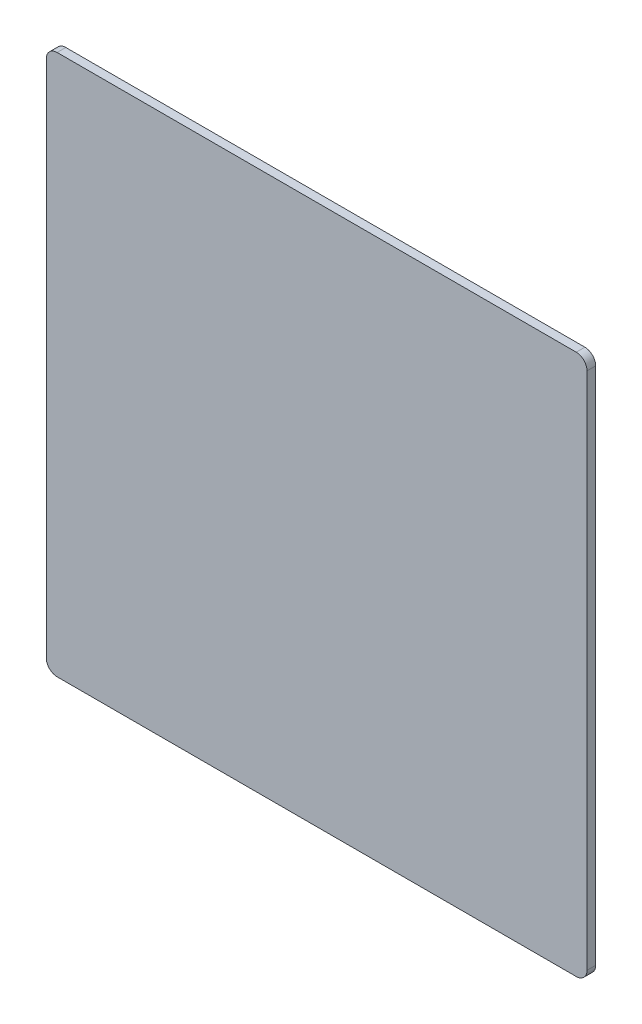
SolidWorks part; units mm, degrees
ref_plane "前视基准面" through (0, 0, 0) normal (0, 0, 1) x (1, 0, 0)
ref_plane "上视基准面" through (0, 0, 0) normal (0, 1, 0) x (1, 0, 0)
ref_plane "右视基准面" through (0, 0, 0) normal (1, 0, 0) x (0, 0, -1)
sketch "草图2" plane through (0, 0, 0) normal (0, 0, 1) x (1, 0, 0)
  line L9 (-50, -48) -> (-50, 48)
  line L14 (-48, 50) -> (48, 50)
  line L16 (50, -48) -> (50, 48)
  line L18 (-48, -50) -> (48, -50)
  arc A0 (-50, 48) -> (-48, 50) centre (-48, 48) cw
  arc A1 (50, 48) -> (48, 50) centre (48, 48) ccw
  arc A2 (50, -48) -> (48, -50) centre (48, -48) cw
  arc A3 (-50, -48) -> (-48, -50) centre (-48, -48) ccw
  point P16 (50, 0)
  point P20 (-50, 0)
extrude "凸台-拉伸1" add sketch "草图2" along normal blind 1.6
ref_plane "基准面4" through (50, 0, 0) normal (1, 0, 0) x (0, 0, -1)
sketch "草图3" plane through (50, 0, 0) normal (1, 0, 0) x (0, 0, -1)
  line L1 (-1.6, -48) -> (-1.6, 48) construction
  line L2 (-1.6, -33.82) -> (-8.9, -33.82)
  line L3 (-8.9, -33.82) -> (-8.9, -41.07)
  line L4 (-8.9, -41.07) -> (-1.6, -41.07)
